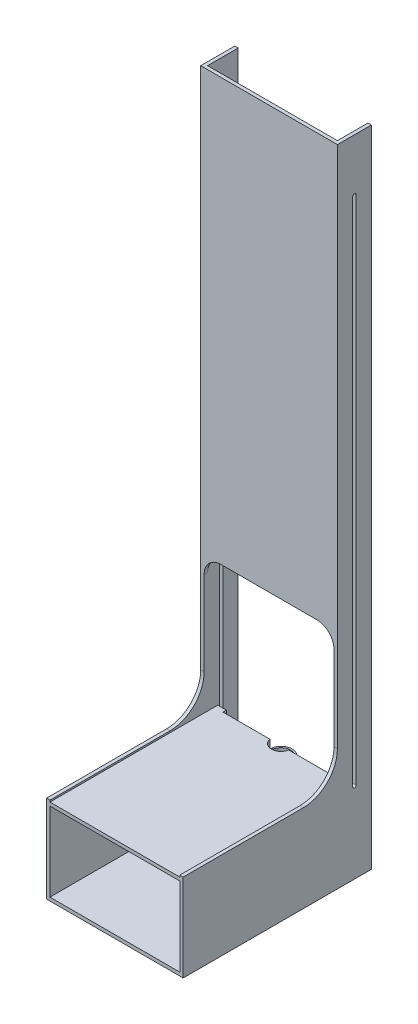
SolidWorks part; units mm, degrees
material "AISI 4340 Steel, annealed"
ref_plane "Front Plane" through (0, 0, 0) normal (0, 0, 1) x (1, 0, 0)
ref_plane "Top Plane" through (0, 0, 0) normal (0, 1, 0) x (1, 0, 0)
ref_plane "Right Plane" through (0, 0, 0) normal (1, 0, 0) x (0, 0, -1)
ref_plane "Right side of elevator platform" through (190.5, 0, 0) normal (1, 0, 0) x (0, 0, -1)
sketch "Sketch2" plane through (190.5, 0, 0) normal (1, 0, 0) x (0, 0, -1)
  line L0 (50, 236.5) -> (50, 1736.5) construction
  line L1 (45, 236.5) -> (45, 1736.5)
  line L2 (55, 236.5) -> (55, 1736.5)
  line L4 (0, 0) -> (100, 0)
  line L5 (0, 0) -> (0, 1800)
  line L6 (0, 1800) -> (100, 1800)
  line L7 (100, 0) -> (100, 1800)
  arc A0 (45, 236.5) -> (55, 236.5) centre (50, 236.5) ccw
  arc A1 (55, 1736.5) -> (45, 1736.5) centre (50, 1736.5) ccw
  point P2 (50, 986.5)
  dimension "D6" = 5
  dimension "D1" = 1800
  dimension "D2" = 100
  dimension "D3" = 50
  dimension "D4" = 236.5
  dimension "D5" = 63.5
extrude "Right side guide" add sketch "Sketch2" along normal blind 10
sketch "Sketch3" plane through (190.5, 0, 0) normal (-1, 0, 0) x (0, 0, 1)
  line L0 (0, 1800) -> (0, 0) construction
  line L1 (-100, 0) -> (0, 0)
  line L2 (-100, 0) -> (-100, 10)
  line L3 (-100, 10) -> (0, 10)
  line L4 (0, 0) -> (0, 10)
  dimension "D1" = 10
extrude "Bottom connection" add sketch "Sketch3" along normal blind 381
sketch "Sketch4" plane through (-190.5, 0, 0) normal (-1, 0, 0) x (0, 0, 1)
  line L0 (-55, 236.5) -> (-55, 1736.5) construction
  line L1 (-45, 1736.5) -> (-45, 236.5) construction
  line L2 (-55, 236.5) -> (-55, 1736.5)
  line L3 (-45, 1736.5) -> (-45, 236.5)
  line L4 (-100, 10) -> (0, 10)
  line L5 (0, 10) -> (0, 1800)
  line L6 (0, 1800) -> (-100, 1800)
  line L7 (-100, 1800) -> (-100, 10)
  line L9 (0, 10) -> (0, 1800)
  line L10 (0, 1800) -> (-100, 1800)
  line L11 (-100, 1800) -> (-100, 10)
  line L16 (-100, 10) -> (-100, 0)
  line L17 (-100, 0) -> (0, 0)
  line L18 (0, 0) -> (0, 10)
  line L19 (0, 10) -> (-100, 10)
  line L20 (-100, 10) -> (-100, 0)
  line L21 (-100, 0) -> (0, 0)
  line L22 (0, 0) -> (0, 10)
  arc A0 (-45, 1736.5) -> (-55, 1736.5) centre (-50, 1736.5) ccw construction
  arc A1 (-55, 236.5) -> (-45, 236.5) centre (-50, 236.5) ccw construction
  arc A2 (-45, 1736.5) -> (-55, 1736.5) centre (-50, 1736.5) ccw
  arc A3 (-55, 236.5) -> (-45, 236.5) centre (-50, 236.5) ccw
  dimension "D1" = 0
  dimension "D2" = 0
extrude "Left side guide" add sketch "Sketch4" along normal blind 10
sketch "Sketch5" plane through (0, 0, 0) normal (0, 0, 1) x (1, 0, 0)
  line L0 (-190.5, 10) -> (-190.5, 1800) construction
  line L1 (-190.5, 1800) -> (190.5, 1800)
  line L2 (-190.5, 1800) -> (-190.5, 653.8)
  line L3 (-190.5, 653.8) -> (190.5, 653.8)
  line L4 (190.5, 1800) -> (190.5, 653.8)
  line L5 (190.5, 1800) -> (190.5, 10) construction
  line L6 (200.5, 1800) -> (190.5, 1800) construction
  line L7 (-190.5, 10) -> (190.5, 10) construction
  dimension "D1" = 643.8
extrude "Structural webbing extrude" add sketch "Sketch5" against normal blind 10
sketch "Sketch6" plane through (0, 0, 0) normal (0, 0, 1) x (1, 0, 0)
  line L0 (-200.5, 251.5) -> (-200.5, 0)
  line L1 (-200.5, 0) -> (-200.5, 1800) construction
  line L2 (-200.5, 0) -> (200.5, 0)
  line L3 (200.5, 0) -> (200.5, 251.5)
  line L4 (200.5, 1800) -> (200.5, 0) construction
  line L5 (200.5, 251.5) -> (190.5, 251.5)
  line L6 (190.5, 653.8) -> (190.5, 10) construction
  line L7 (190.5, 251.5) -> (190.5, 10)
  line L8 (190.5, 10) -> (-190.5, 10)
  line L9 (-190.5, 10) -> (-190.5, 251.5)
  line L10 (-190.5, 10) -> (-190.5, 653.8) construction
  line L11 (-190.5, 251.5) -> (-200.5, 251.5)
  dimension "D1" = 241.5
extrude "Input roller holder extrude" add sketch "Sketch6" along normal blind 452.52
sketch "Sketch7" plane through (190.5, 0, 0) normal (-1, 0, 0) x (0, 0, 1)
  line L0 (0, 653.8) -> (0, 251.5) construction
  line L1 (452.52, 251.5) -> (-40, 251.5)
  line L2 (452.52, 251.5) -> (452.52, 241.5)
  line L3 (452.52, 241.5) -> (-40, 241.5)
  line L4 (-40, 251.5) -> (-40, 241.5)
  dimension "D1" = 40
  dimension "D2" = 10
extrude "Input roller platform" add sketch "Sketch7" along normal up to next
sketch "Sketch8" plane through (0, 251.5, 0) normal (0, 1, 0) x (1, 0, 0)
  line L1 (-200.5, -452.52) -> (-190.5, -452.52)
  line L2 (-200.5, -452.52) -> (-200.5, 0)
  line L3 (-200.5, 0) -> (-190.5, 0)
  line L4 (-190.5, -452.52) -> (-190.5, 0)
  line L5 (190.5, 0) -> (200.5, 0)
  line L6 (190.5, 0) -> (190.5, -452.52)
  line L7 (190.5, -452.52) -> (200.5, -452.52)
  line L8 (200.5, 0) -> (200.5, -452.52)
extrude "Siding outline" add sketch "Sketch8" along normal blind 5
sketch "Sketch9" plane through (0, 1800, 0) normal (0, 1, 0) x (1, 0, 0)
  line L8 (190.5, 100) -> (190.5, 10)
  line L9 (190.5, 10) -> (-190.5, 10)
  line L10 (-190.5, 10) -> (-190.5, 100)
  line L11 (-190.5, 100) -> (-200.5, 100)
  line L12 (-200.5, 100) -> (-200.5, 0)
  line L13 (-200.5, 0) -> (200.5, 0)
  line L14 (200.5, 0) -> (200.5, 100)
  line L15 (200.5, 100) -> (190.5, 100)
  line L16 (190.5, 100) -> (190.5, 10)
  line L17 (190.5, 10) -> (-190.5, 10)
  line L18 (-190.5, 10) -> (-190.5, 100)
  line L19 (-190.5, 100) -> (-200.5, 100)
  line L20 (-200.5, 100) -> (-200.5, 0)
  line L21 (-200.5, 0) -> (200.5, 0)
  line L22 (200.5, 0) -> (200.5, 100)
  line L23 (200.5, 100) -> (190.5, 100)
  dimension "D1" = 0
extrude "Lip to prevent box from falling out" add sketch "Sketch9" along normal blind 91.5
fillet "Vertical section fillets" radius 100 2 edges at (195.5, 256.5, 0) (-195.5, 256.5, 0)
fillet "Smaller fillets" radius 50 2 edges at (190.5, 653.8, -5) (-190.5, 653.8, -5)
sketch "Sketch11" plane through (0, 0, -40) normal (0, 0, -1) x (-1, 0, 0)
  line L0 (190.5, 251.5) -> (-190.5, 251.5) construction
  line L1 (-165.5, 251.5) -> (165.5, 251.5)
  line L2 (-165.5, 251.5) -> (-165.5, 241.5)
  line L3 (-165.5, 241.5) -> (165.5, 241.5)
  line L4 (165.5, 251.5) -> (165.5, 241.5)
  line L5 (190.5, 241.5) -> (-190.5, 241.5) construction
  line L6 (-190.5, 251.5) -> (-190.5, 241.5) construction
  line L7 (190.5, 251.5) -> (190.5, 241.5) construction
  dimension "D1" = 25
  dimension "D2" = 25
extrude "Gate spacing cut" cut sketch "Sketch11" against normal blind 10
sketch "Sketch12" plane through (-190.5, 0, 0) normal (1, 0, 0) x (0, 0, -1)
  line L1 (45, 221.5) -> (40, 221.5)
  line L2 (45, 221.5) -> (45, 10)
  line L3 (45, 10) -> (40, 10)
  line L4 (40, 221.5) -> (40, 10)
  line L5 (100, 1891.5) -> (100, 10) construction
  line L6 (45, 236.5) -> (45, 1736.5) construction
  line L7 (-452.52, 10) -> (100, 10) construction
  line L8 (40, 241.5) -> (-452.52, 241.5) construction
  line L9 (30, 241.5) -> (25, 241.5)
  line L10 (30, 241.5) -> (30, 10)
  line L11 (30, 10) -> (25, 10)
  line L12 (25, 241.5) -> (25, 10)
  dimension "D1" = 60
  dimension "D2" = 20
  dimension "D3" = 5
extrude "Gate guide rails" add sketch "Sketch12" along normal up to next
sketch "Sketch13" plane through (0, 0, -45) normal (0, 0, -1) x (-1, 0, 0)
  line L0 (-190.5, 221.5) -> (190.5, 221.5) construction
  line L1 (-150.5, 221.5) -> (150.5, 221.5)
  line L2 (-150.5, 221.5) -> (-150.5, 10)
  line L3 (-150.5, 10) -> (150.5, 10)
  line L4 (150.5, 221.5) -> (150.5, 10)
  line L5 (190.5, 10) -> (-190.5, 10) construction
  line L6 (-190.5, 10) -> (-190.5, 1891.5) construction
  point P8 (0, 221.5)
  dimension "D1" = 40
extrude "Gate rod connection cutout" cut sketch "Sketch13" against normal through all
sketch "Sketch14" plane through (0, 10, 0) normal (0, 1, 0) x (1, 0, 0)
  line L0 (150.5, 45) -> (-150.5, 25) construction
  circle A0 centre (0, 35) radius 28
  circle A1 centre (0, 35) radius 33
  point P7 (0, 35)
  dimension "D1" = 56
  dimension "D2" = 5
extrude "Spring cup" add sketch "Sketch14" along normal blind 75
sketch "Sketch15" plane through (0, 85, 0) normal (0, 1, 0) x (1, 0, 0)
  line L0 (190.5, 30) -> (150.5, 30) construction
  line L1 (32.619, 30) -> (27.55, 30)
  line L3 (32.619, 40) -> (27.55, 40)
  line L5 (-27.55, 40) -> (-32.619, 40)
  line L6 (-27.55, 30) -> (-32.619, 30)
  circle A0 centre (0, 35) radius 28 construction
  arc A1 (27.55, 40) -> (-27.55, 40) centre (0, 35) ccw
  circle A2 centre (0, 35) radius 33 construction
  arc A3 (32.619, 40) -> (-32.619, 40) centre (0, 35) ccw
  arc A4 (-27.55, 30) -> (27.55, 30) centre (0, 35) ccw
  arc A5 (-32.619, 30) -> (32.619, 30) centre (0, 35) ccw
extrude "Spring container extension" add sketch "Sketch15" along normal up to surface (136.5 mm away) up to face at (0, 221.5, -27.5)
sketch "Sketch16" plane through (0, 221.5, 0) normal (0, 1, 0) x (1, 0, 0)
  circle A0 centre (0, 35) radius 28
  arc A1 (27.55, 40) -> (-27.55, 40) centre (0, 35) ccw construction
extrude "Spring hole (can't insert spring without this)" cut sketch "Sketch16" along normal up to surface (30 mm away) up to face at (0, 251.5, 85.63)
sketch "Sketch17" plane through (0, 221.5, 0) normal (0, 1, 0) x (1, 0, 0)
  line L2 (-26.1534, 25) -> (-31.4484, 25)
  line L3 (31.4484, 25) -> (26.1534, 25)
  line L4 (-26.1534, 25) -> (-31.4484, 25)
  line L5 (31.4484, 25) -> (26.1534, 25)
  arc A2 (-31.4484, 25) -> (31.4484, 25) centre (0, 35) ccw
  arc A3 (-26.1534, 25) -> (26.1534, 25) centre (0, 35) ccw
  arc A4 (-31.4484, 25) -> (31.4484, 25) centre (0, 35) ccw
  arc A5 (-26.1534, 25) -> (26.1534, 25) centre (0, 35) ccw
  dimension "D1" = 0
extrude "Container extension to meet with conveyor plate" add sketch "Sketch17" along normal up to next
fillet "Spring holder fillets" radius 10 4 edges at (0, 10, -68) (-31.4484, 231.5, -25) (31.4484, 231.5, -25) (0, 241.5, -2)
